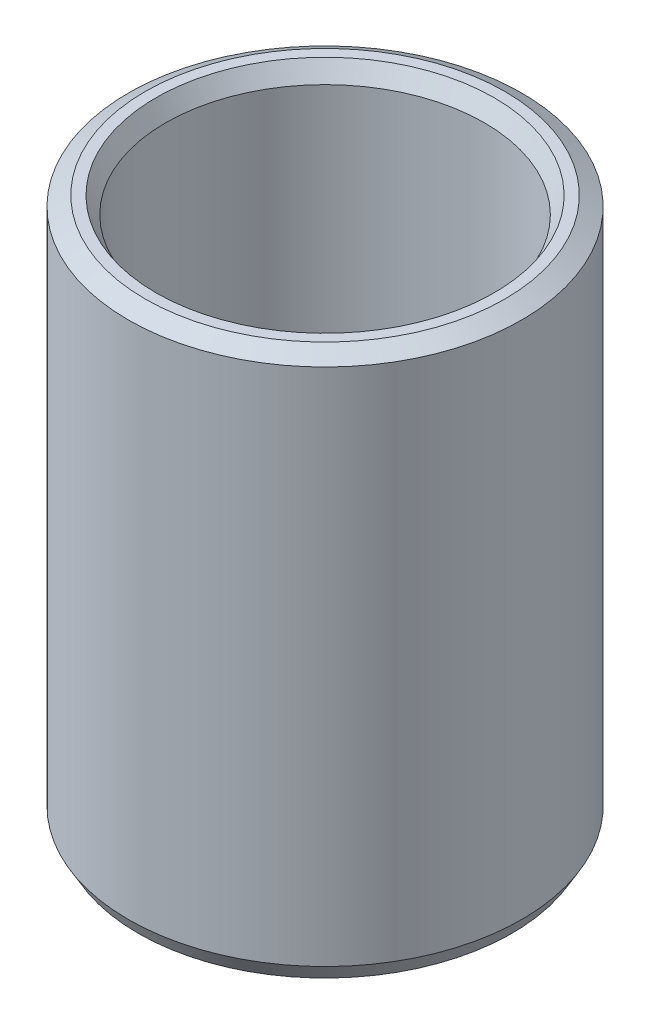
SolidWorks part; units mm, degrees
ref_plane "Front Plane" through (0, 0, 0) normal (0, 0, 1) x (1, 0, 0)
ref_plane "Top Plane" through (0, 0, 0) normal (0, 1, 0) x (1, 0, 0)
ref_plane "Right Plane" through (0, 0, 0) normal (1, 0, 0) x (0, 0, -1)
sketch "Sketch1" plane through (0, 0, 0) normal (0, 1, 0) x (1, 0, 0)
  circle A0 centre (0, 0) radius 50
  dimension "SLEEVE_OD" = 100
extrude "Boss-Extrude1" add sketch "Sketch1" along normal blind 138.7709
sketch "Sketch2" plane through (0, 0, 0) normal (0, 1, 0) x (1, 0, 0)
  circle A0 centre (0, 0) radius 40.5134
  dimension "BORE_D" = 81.0268
extrude "Cut-Extrude1" cut sketch "Sketch2" along normal through all
chamfer "Chamfer1" distance 2.4718 angle 60 4 edges at (0, 138.7709, 40.5134) (0, 0, 40.5134) (0, 0, 50) (0, 138.7709, 50) first distance on face at (0, 138.7709, 40.5134) first distance on face at (0, 0, 40.5134) first distance on face at (0, 138.7709, 50)
